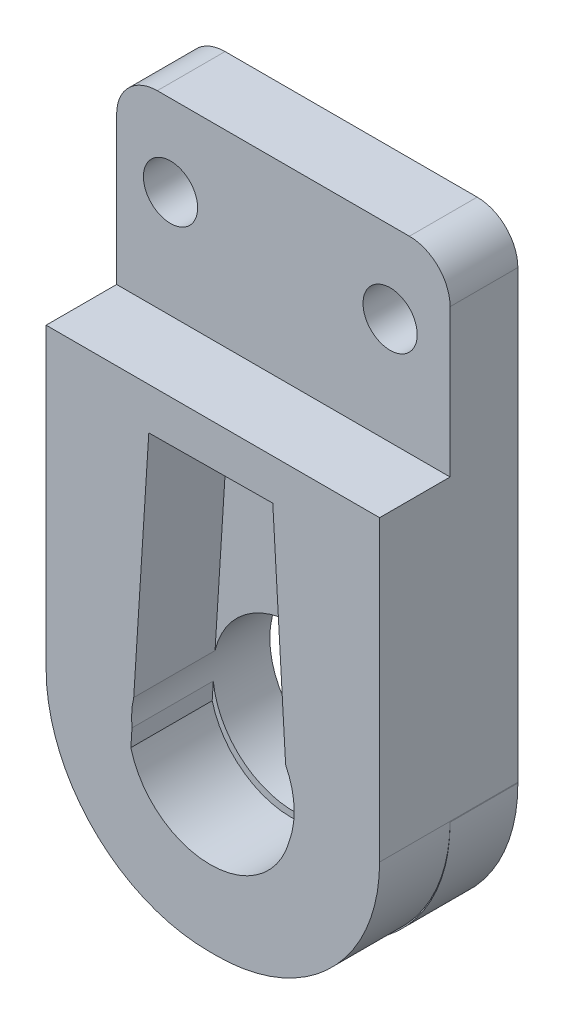
SolidWorks part; units mm, degrees
ref_plane "Front Plane" through (0, 0, 0) normal (0, 0, 1) x (1, 0, 0)
ref_plane "Top Plane" through (0, 0, 0) normal (0, 1, 0) x (1, 0, 0)
ref_plane "Right Plane" through (0, 0, 0) normal (1, 0, 0) x (0, 0, -1)
other "Graphic1"
ref_plane "Plane2" through (0, 0, 10) normal (0, 0, 1) x (1, 0, 0)
sketch "Sketch2" plane through (0, 0, 10) normal (0, 0, 1) x (1, 0, 0)
  line L1 (-326.0372, 240.3637) -> (-313.7372, 240.3637)
  line L2 (-326.0372, 240.3637) -> (-326.0372, 216.3637)
  line L3 (-326.0372, 216.3637) -> (-313.7372, 216.3637)
  line L4 (-313.7372, 240.3637) -> (-313.7372, 216.3637)
  dimension "D1" = 12.3
  dimension "D2" = 24
extrude "Boss-Extrude1" add sketch "Sketch2" along normal blind 2.5
fillet "Fillet1" radius 6 2 edges at (-313.7372, 216.3637, 11.25) (-326.0372, 216.3637, 11.25)
fillet "Fillet2" radius 1.5 2 edges at (-326.0372, 240.3637, 11.25) (-313.7372, 240.3637, 11.25)
sketch "Sketch3" plane through (0, 0, 12.5) normal (0, 0, 1) x (1, 0, 0)
  line L0 (-315.2372, 240.3637) -> (-324.5372, 240.3637) construction
  circle A0 centre (-324.0491, 237.3637) radius 1
  circle A1 centre (-315.9491, 237.3637) radius 1
  dimension "D1" = 2
  dimension "D2" = 2
  dimension "D3" = 8.1
  dimension "D4" = 3
extrude "Cut-Extrude1" cut sketch "Sketch3" against normal blind 3.5
ref_plane "Plane3" through (0, 0, 12.5) normal (0, 0, 1) x (1, 0, 0)
sketch "Sketch4" plane through (0, 0, 12.5) normal (0, 0, 1) x (1, 0, 0)
  line L0 (-326.0372, 238.8637) -> (-326.0372, 222.3637) construction
  line L1 (-326.0372, 233.4227) -> (-313.7372, 233.4227)
  line L2 (-326.0372, 233.4227) -> (-326.0372, 216.4227)
  line L3 (-326.0372, 216.4227) -> (-313.7372, 216.4227)
  line L4 (-313.7372, 233.4227) -> (-313.7372, 216.4227)
  dimension "D1" = 17
  dimension "D2" = 12.3
extrude "Boss-Extrude2" add sketch "Sketch4" along normal blind 2.6
sketch "Sketch5" plane through (0, 0, 15.1) normal (0, 0, 1) x (1, 0, 0)
  line L0 (-319.8872, 233.4227) -> (-319.8872, 211.9352) construction
  line L1 (-313.7372, 233.4227) -> (-326.0372, 233.4227) construction
  circle A0 centre (-319.8872, 222.4539) radius 3
  dimension "D1" = 6
extrude "Cut-Extrude2" cut sketch "Sketch5" against normal through all
sketch "Sketch6" plane through (0, 0, 15.1) normal (0, 0, 1) x (1, 0, 0)
  line L0 (-322.2509, 231.8753) -> (-317.6776, 231.9162)
  line L1 (-317.6776, 231.9162) -> (-317.0657, 221.4345)
  line L2 (-322.2509, 231.8753) -> (-322.9124, 221.4882)
  circle A0 centre (-319.8872, 222.4539) radius 3 construction
  arc A1 (-322.9124, 221.4882) -> (-317.0657, 221.4345) centre (-319.9819, 222.2419) ccw
extrude "Cut-Extrude3" cut sketch "Sketch6" against normal blind 3
fillet "Fillet3" radius 6 2 edges at (-326.0372, 216.4227, 13.8) (-313.7372, 216.4227, 13.8)
